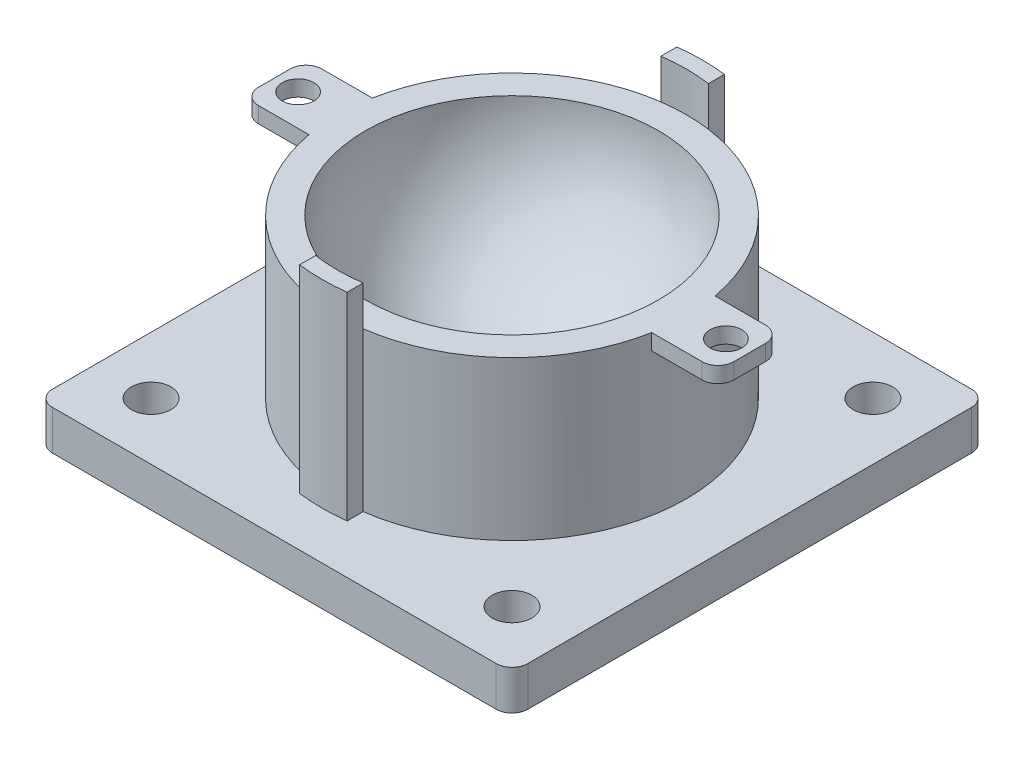
SolidWorks part; units mm, degrees
note: The reader was unsure of these and kept them because the rebuilt part matched: shared geometry of "Sketch1<3>".
ref_plane "Front Plane" through (0, 0, 0) normal (0, 0, 1) x (1, 0, 0)
ref_plane "Top Plane" through (0, 0, 0) normal (0, 1, 0) x (1, 0, 0)
ref_plane "Right Plane" through (0, 0, 0) normal (1, 0, 0) x (0, 0, -1)
sketch "Sketch1" plane through (0, 0, 0) normal (0, 1, 0) x (1, 0, 0)
  line L0 (-30, -30) -> (-24.5459, -24.5459) construction
  line L1 (-30, -30) -> (30, -30)
  line L2 (-30, -30) -> (-30, 30)
  line L3 (-30, 30) -> (30, 30)
  line L4 (30, -30) -> (30, 30)
  line L5 (-30, -30) -> (30, 30) construction
  line L6 (-30, 30) -> (30, -30) construction
  line L7 (-21.0104, -21.0104) -> (-15.5563, -15.5563) construction
  line L8 (-9.2513, 0) -> (9.2513, 0) construction
  circle A0 centre (0, 0) radius 18.5
  circle A1 centre (0, 0) radius 22
  circle A2 centre (-22.7782, -22.7782) radius 2.5
  circle A3 centre (22.7782, -22.7782) radius 2.5
  circle A4 centre (22.7782, 22.7782) radius 2.5
  circle A5 centre (-22.7782, 22.7782) radius 2.5
  point P0 (0, 0)
  dimension "D3" = 37
  dimension "D4" = 3.5
  dimension "D5" = 5
  dimension "D6" = 5
  dimension "D1" = 60
  dimension "D2" = 60
extrude "Boss-Extrude1" add sketch "Sketch1" along normal blind 5 contours L1 L4 L3 L2 A4 A3 A2 A1 A5 | A0 | A1 A0
extrude "Boss-Extrude2" add sketch "Sketch1<3>" along normal blind 20 from surface at 5 contours A1 A0 | A0 starting at face at (22.7782, 5, -20.2782)
sketch "Sketch1<3>" plane through (0, 0, 0) normal (0, 1, 0) x (1, 0, 0) same geometry as "Sketch1"
sketch "Sketch3" plane through (0, 0, 0) normal (0, 0, 1) x (1, 0, 0)
  line L0 (22, 25) -> (-22, 25) construction
  line L1 (22, 25) -> (-22, 25)
  line L2 (0, 6.5) -> (0, 25) construction
  line L3 (-18.5, 25) -> (0, 25)
  line L4 (-18.5, 25) -> (-18.5, 16.0015)
  line L5 (-18.5, 16.0015) -> (0, 16.0015)
  line L6 (0, 16.0015) -> (0, 25)
  arc A0 (-18.5, 25) -> (0, 6.5) centre (0, 25) ccw
  point P5 (0, 25)
  dimension "D1" = 18.5
revolve "Cut-Revolve4" cut sketch "Sketch3" angle 360 about L2
fillet "Fillet1" radius 2 4 edges at (-30, 2.5, -30) (30, 2.5, -30) (30, 2.5, 30) (-30, 2.5, 30)
sketch "Sketch4" plane through (0, 5, 0) normal (0, 1, 0) x (1, 0, 0)
  line L0 (-28, -30) -> (28, -30) construction
  line L1 (-3, 30) -> (3, 30)
  line L2 (-3, 30) -> (-3, -30)
  line L3 (-3, -30) -> (3, -30)
  line L4 (3, 30) -> (3, -30)
  line L5 (-3, 30) -> (3, -30) construction
  line L6 (-3, -30) -> (3, 30) construction
  circle A0 centre (0, 0) radius 22 construction
  circle A1 centre (0, 0) radius 22
  circle A2 centre (0, 0) radius 24
  circle M4 centre (0, 0) radius 22
  dimension "D2" = 6
  dimension "D1" = 2
extrude "Boss-Extrude6" add sketch "Sketch4" along direction (0, 1, 0) on the side of the normal blind 25 contours L4 A2 L2 M4 | L2 A2 L4 M4
sketch "Sketch5" plane through (0, 25, 0) normal (0, 1, 0) x (1, 0, 0)
  line L0 (0, -55) -> (0, 55) construction
  line L1 (28, 4) -> (-28, 4)
  line L2 (30, 2) -> (30, -2)
  line L3 (28, -4) -> (-28, -4)
  line L4 (-30, 2) -> (-30, -2)
  line L5 (30, 4) -> (-30, -4) construction
  line L6 (30, -4) -> (-30, 4) construction
  arc A0 (-3, 21.7945) -> (-3, -21.7945) centre (0, 0) ccw construction
  arc A1 (3, -21.7945) -> (3, 21.7945) centre (0, 0) ccw construction
  arc A2 (-3, 21.7945) -> (-3, -21.7945) centre (0, 0) ccw
  arc A3 (3, -21.7945) -> (3, 21.7945) centre (0, 0) ccw
  circle A4 centre (27, 0) radius 2
  circle A5 centre (-27, 0) radius 2
  arc A6 (-28, 4) -> (-30, 2) centre (-28, 2) ccw
  arc A7 (-28, -4) -> (-30, -2) centre (-28, -2) cw
  arc A8 (30, -2) -> (28, -4) centre (28, -2) cw
  arc A9 (28, 4) -> (30, 2) centre (28, 2) cw
  point P0 (0, 0)
  arc M10 (-3, 21.7945) -> (-3, -21.7945) centre (0, 0) ccw
  arc M12 (3, -21.7945) -> (3, 21.7945) centre (0, 0) ccw
  dimension "D3" = 4
  dimension "D5" = 2
  dimension "D1" = 60
  dimension "D2" = 8
  dimension "D4" = 3
extrude "Boss-Extrude7" add sketch "Sketch5" against normal blind 2 contours A9 L1 L3 A8 L2 A4 M12 | A7 L3 L1 A6 L4 A5 M10
